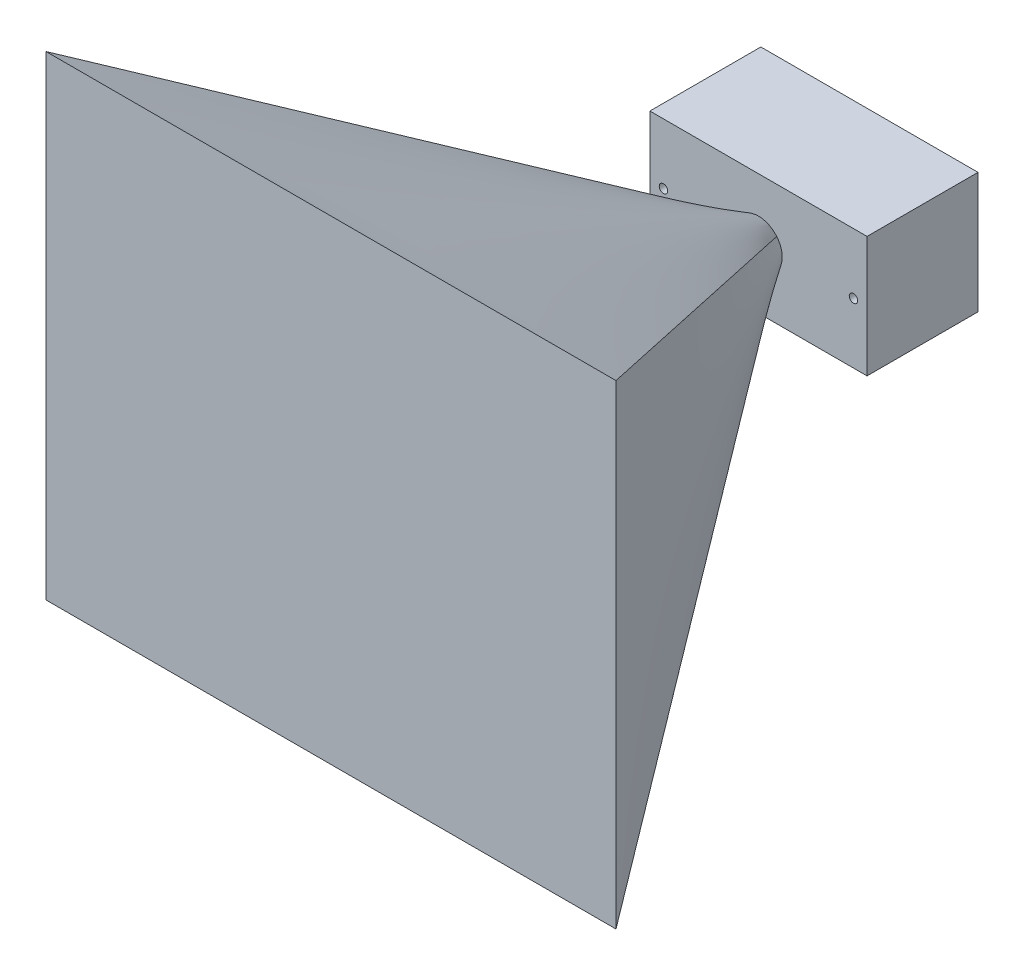
SolidWorks part; units mm, degrees
ref_plane "Front Plane" through (0, 0, 0) normal (0, 0, 1) x (1, 0, 0)
ref_plane "Top Plane" through (0, 0, 0) normal (0, 1, 0) x (1, 0, 0)
ref_plane "Right Plane" through (0, 0, 0) normal (1, 0, 0) x (0, 0, -1)
ref_plane "small camera plane" through (0, 0, 114.3) normal (0, 0, 1) x (1, 0, 0)
ref_plane "large camera plane" through (0, 0, 25400) normal (0, 0, 1) x (1, 0, 0)
sketch "small camera sketch" plane through (0, 0, 114.3) normal (0, 0, 1) x (1, 0, 0)
  line L1 (-76.2, -63.5) -> (76.2, -63.5)
  line L2 (-76.2, -63.5) -> (-76.2, 63.5)
  line L3 (-76.2, 63.5) -> (76.2, 63.5)
  line L4 (76.2, -63.5) -> (76.2, 63.5)
  line L5 (-76.2, -63.5) -> (76.2, 63.5) construction
  line L6 (-76.2, 63.5) -> (76.2, -63.5) construction
  point P0 (0, 0)
  dimension "D1" = 152.4
  dimension "D2" = 127
sketch "large camera sketch" plane through (0, 0, 25400) normal (0, 0, 1) x (1, 0, 0)
  line L1 (-18135.6, -15138.4) -> (18135.6, -15138.4)
  line L2 (-18135.6, -15138.4) -> (-18135.6, 15138.4)
  line L3 (-18135.6, 15138.4) -> (18135.6, 15138.4)
  line L4 (18135.6, -15138.4) -> (18135.6, 15138.4)
  line L5 (-18135.6, -15138.4) -> (18135.6, 15138.4) construction
  line L6 (-18135.6, 15138.4) -> (18135.6, -15138.4) construction
  point P0 (0, 0)
  dimension "D1" = 36271.2
  dimension "D2" = 30276.8
sketch "camera front hole" plane through (0, 0, 0) normal (0, 0, 1) x (1, 0, 0)
  circle A0 centre (0, 0) radius 6.35
loft "field of view" add profiles "camera front hole", "small camera sketch" connector at (6.35, 0, 0) connector at (76.2, 63.5, 114.3)
sketch "Sketch4" plane through (0, 0, 0) normal (0, 0, -1) x (-1, 0, 0)
  line L1 (29.0322, 16.1544) -> (-29.0322, 16.1544)
  line L2 (29.0322, 16.1544) -> (29.0322, -16.1544)
  line L3 (29.0322, -16.1544) -> (-29.0322, -16.1544)
  line L4 (-29.0322, 16.1544) -> (-29.0322, -16.1544)
  line L5 (29.0322, 16.1544) -> (-29.0322, -16.1544) construction
  line L6 (29.0322, -16.1544) -> (-29.0322, 16.1544) construction
  point P0 (0, 0)
  dimension "D1" = 58.0644
  dimension "D2" = 32.3088
extrude "camera body" add sketch "Sketch4" along normal blind 29.6672
hole_wizard "#4-40 mount holes" positions "Sketch6" profile "Sketch5" tap size "#4-40" standard "ANSI Inch" end condition up to next
sketch "Sketch6" plane through (0, 0, -29.6672) normal (0, 0, -1) x (-1, 0, 0)
  point P0 (-25.4, 0)
  point P2 (25.4, 0)
  dimension "D1" = 25.4
  dimension "D2" = 25.4
sketch "Sketch5" plane through (25.4, 0, -29.6672) normal (1, 0, 0) x (0, 1, 0)
  line L0 (0, 0) -> (0, 29.6672)
  line L1 (0, 29.6672) -> (1.1303, 29.6672)
  line L2 (1.1303, 29.6672) -> (1.1303, 0)
  line L5 (1.1303, 0) -> (0, 0)
  line L11 (0, -6.35) -> (0, 107.95) construction
  dimension "Thread Major Dia." = 2.2606
  dimension "Thru Tap Drill Depth" = 29.6672
sketch "reference sketches" plane through (0, 0, 0) normal (0, 0, 1) x (1, 0, 0)
  line L0 (29.0322, 16.1544) -> (29.0322, -16.1544) construction
  line L1 (-29.0322, 16.1544) -> (29.0322, 16.1544) construction
  point P0 (29.0322, 0)
  point P1 (-0.4082, 16.1544)
ref_point "z-basis"
ref_point "y-basis"
ref_point "centre of vision"
ref_point "direction reference"
